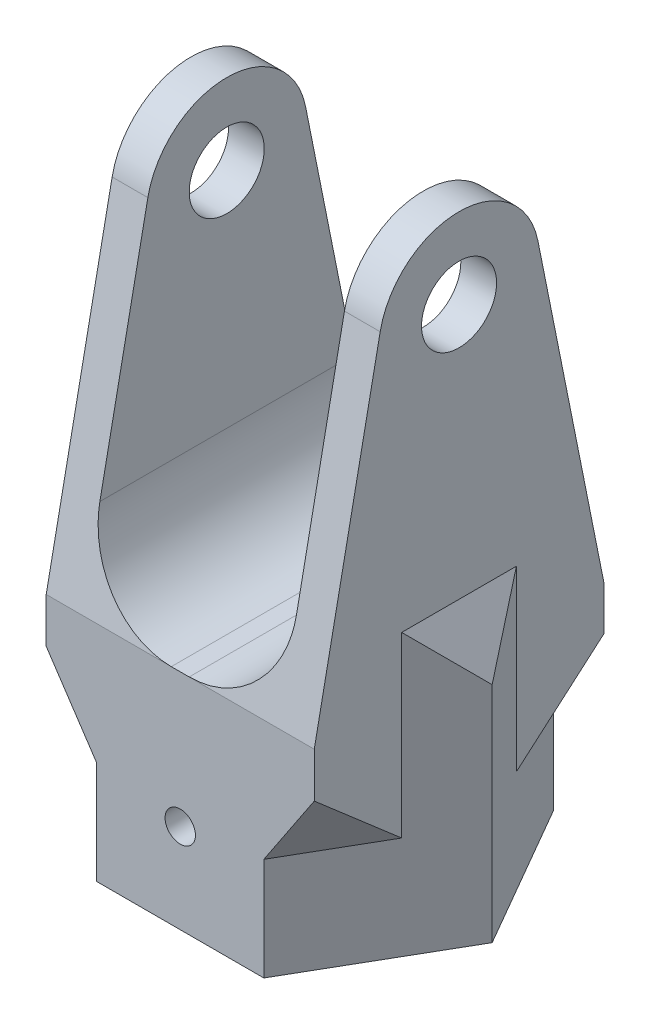
SolidWorks part; units mm, degrees
ref_plane "Alzado" through (0, 0, 0) normal (0, 0, 1) x (1, 0, 0)
ref_plane "Planta" through (0, 0, 0) normal (0, 1, 0) x (1, 0, 0)
ref_plane "Vista lateral" through (0, 0, 0) normal (1, 0, 0) x (0, 0, -1)
sketch "Croquis1" plane through (0, 0, 0) normal (1, 0, 0) x (0, 0, -1)
  line L0 (-13, 0) -> (13, 0)
  line L1 (13, 0) -> (13, -20)
  line L2 (13, -20) -> (16.2, -20)
  line L3 (16.2, -20) -> (16.2, 0)
  line L4 (0, 0) -> (0, 35) construction
  line L5 (16.2, 0) -> (8.8242, 36.7701)
  line L6 (-16.2, 0) -> (-8.8242, 36.7701)
  line L7 (-16.2, -20) -> (-16.2, 0)
  line L8 (-13, -20) -> (-16.2, -20)
  line L9 (-13, 0) -> (-13, -20)
  line L10 (-16.2, 0) -> (-13, 0)
  line L11 (13, 0) -> (16.2, 0)
  circle A0 centre (0, 35) radius 4.2
  circle A1 centre (0, 35) radius 9
  dimension "D4" = 8.4
  dimension "D5" = 18
  dimension "D1" = 35
  dimension "D2" = 20
  dimension "D3" = 3.2
  dimension "D6" = 13
extrude "Saliente-Extruir1" add sketch "Croquis1" along normal blind 4 from offset 11 contours L0 L4 A1 L6 L10 | L4 L0 L11 L5 A1 | A1 A0 region at (0, 13.3356, 6.9565) region at (0, 13.3356, -6.9565) region at (0, 29.4574, 6.7648)
extrude "Saliente-Extruir2" add sketch "Croquis1<3>" against normal blind 4 from offset 11 separate body contours L0 L4 A1 L6 L10 | L4 L0 L11 L5 A1 | A1 A0 region at (0, 13.3356, 6.9565) region at (0, 13.3356, -6.9565) region at (0, 29.4574, 6.7648) offset against normal yes
sketch "Croquis1<3>" plane through (0, 0, 0) normal (1, 0, 0) x (0, 0, -1) same geometry as "Croquis1"
sketch "Croquis2" plane through (0, 0, 0) normal (0, 1, 0) x (1, 0, 0)
  line L0 (11, 16.2) -> (9.3531, 16.2) construction
  line L1 (9.3531, 16.2) -> (-9.3531, 16.2)
  line L2 (-9.3531, 16.2) -> (-18.7061, 0)
  line L3 (-18.7061, 0) -> (-9.3531, -16.2)
  line L4 (-9.3531, -16.2) -> (9.3531, -16.2)
  line L5 (9.3531, -16.2) -> (18.7061, 0)
  line L6 (18.7061, 0) -> (9.3531, 16.2)
  line L7 (9.3531, 16.2) -> (15, 16.2)
  line L8 (15, 16.2) -> (15, 6.4192)
  line L10 (-9.3531, 16.2) -> (-15, 16.2)
  line L11 (-15, 16.2) -> (-15, 6.4192)
  line L12 (-15, -16.2) -> (-15, 16.2) construction
  line L13 (15, -16.2) -> (15, 16.2) construction
  line L14 (9.3531, -16.2) -> (15, -16.2)
  line L15 (15, -16.2) -> (11, -16.2) construction
  line L16 (15, -16.2) -> (15, -6.4192)
  line L17 (-9.3531, -16.2) -> (-15, -16.2)
  line L18 (-15, -16.2) -> (-15, -6.4192)
  circle A0 centre (0, 0) radius 13.1
  circle A2 centre (0, 0) radius 16.2 construction
  dimension "D2" = 26.2
extrude "Saliente-Extruir3" add sketch "Croquis2" against normal blind 5 contours L18 L17 L3 | L14 L16 L5 | L8 L7 L6 | L10 L11 L2 | A0 region at (13.1177, 0, -12.9397) region at (-13.1177, 0, -12.9397) region at (13.1177, 0, 12.9397) region at (-13.1177, 0, 12.9397) region at (0, 0, 0)
extrude "Saliente-Extruir4" add sketch "Croquis2<3>" against normal blind 25 contours L5 L6 L1 L2 L3 L4 A0 region at (11.7479, 0, -11.0622)
sketch "Croquis2<3>" plane through (0, 0, 0) normal (0, 1, 0) x (1, 0, 0) same geometry as "Croquis2"
chamfer "Chaflán1" distance 8.5 angle 30 4 edges at (12.1765, -5, -11.3096) (-12.1765, -5, -11.3096) (-12.1765, -5, 11.3096) (12.1765, -5, 11.3096) first distance on face at (14.3531, -10, -7.5397) first distance on face at (-14.3531, -10, -7.5397) first distance on face at (-14.3531, -10, 7.5397) first distance on face at (14.3531, -10, 7.5397)
chamfer "Chaflán3" distance 6.42 angle 30 1 edges at (-15, 0, 0) first distance on face at (-15, 4.3711, 0)
chamfer "Chaflán4" distance 3.71 angle 60 1 edges at (15, 0, 0) first distance on face at (16.2354, 0, 0)
fillet "Redondeo2" radius 10 2 edges at (-11, 0, 0) (11, 0, 0)
ref_plane "Plano1" through (0, 0, 16.2) normal (0, 0, 1) x (1, 0, 0)
sketch "Croquis3" plane through (0, 0, 16.2) normal (0, 0, 1) x (1, 0, 0)
  line L0 (0, -25) -> (0, -15) construction
  line L1 (-9.3531, -25) -> (9.3531, -25) construction
  circle A0 centre (0, -15) radius 1.7
  dimension "D2" = 3.4
  dimension "D1" = 10
extrude "Cortar-Extruir1" cut sketch "Croquis3" against normal up to surface (32.4 mm away) up to face at (0, -8.7059, -16.2)
